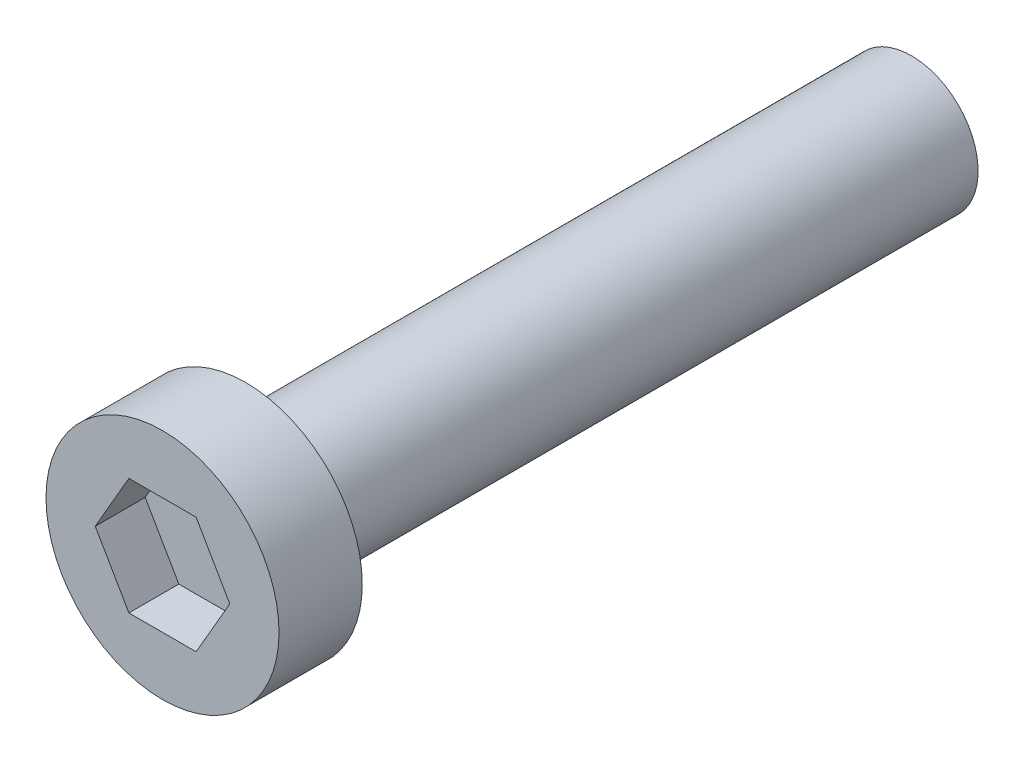
SolidWorks part; units mm, degrees
ref_plane "前视基准面" through (0, 0, 0) normal (0, 0, 1) x (1, 0, 0)
ref_plane "上视基准面" through (0, 0, 0) normal (0, 1, 0) x (1, 0, 0)
ref_plane "右视基准面" through (0, 0, 0) normal (1, 0, 0) x (0, 0, -1)
sketch "草图1" plane through (0, 0, 0) normal (0, 0, 1) x (1, 0, 0)
  line L1 (2.0207, 0) -> (1.0104, 1.75)
  line L2 (1.0104, 1.75) -> (-1.0104, 1.75)
  line L3 (-1.0104, 1.75) -> (-2.0207, 0)
  line L4 (-2.0207, 0) -> (-1.0104, -1.75)
  line L5 (-1.0104, -1.75) -> (1.0104, -1.75)
  line L6 (1.0104, -1.75) -> (2.0207, 0)
  circle A0 centre (0, 0) radius 3.5
  circle A1 centre (0, 0) radius 1.75 construction
  dimension "D1" = 7
  dimension "D2" = 3.5
extrude "凸台-拉伸1" add sketch "草图1" along normal blind 2.5
sketch "草图2" plane through (0, 0, 0) normal (0, 0, -1) x (-1, 0, 0)
  circle A0 centre (0, 0) radius 2
  dimension "D1" = 4
extrude "凸台-拉伸2" add sketch "草图2" along normal blind 20
extrude "凸台-拉伸3" add sketch "草图1<3>" along normal blind 1 from surface contours L5 L6 L1 L2 L3 L4 region at (0, 0, 0) starting at face at (0, 0, 0)
sketch "草图1<3>" plane through (0, 0, 0) normal (0, 0, 1) x (1, 0, 0) same geometry as "草图1"
